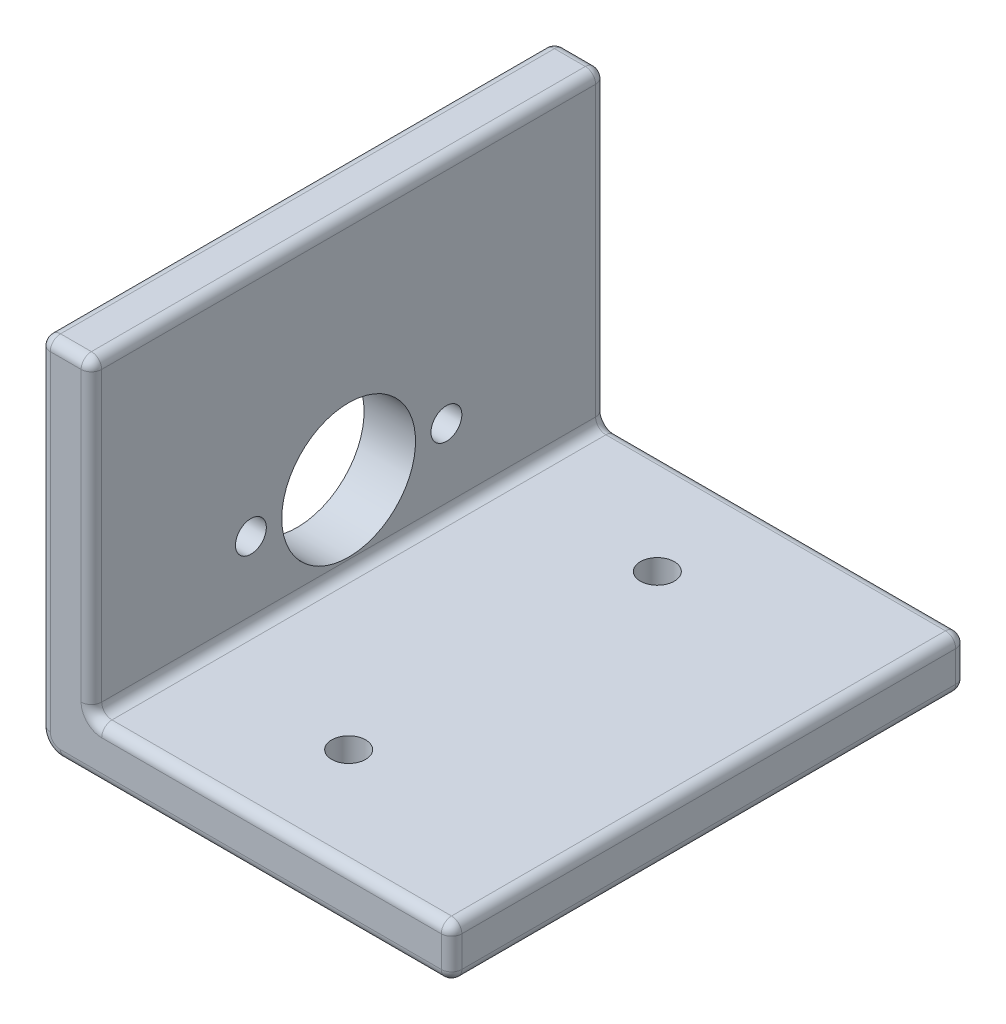
SolidWorks part; units mm, degrees
ref_plane "Front Plane" through (0, 0, 0) normal (0, 0, 1) x (1, 0, 0)
ref_plane "Top Plane" through (0, 0, 0) normal (0, 1, 0) x (1, 0, 0)
ref_plane "Right Plane" through (0, 0, 0) normal (1, 0, 0) x (0, 0, -1)
sketch "Sketch1" plane through (0, 0, 0) normal (0, 0, 1) x (1, 0, 0)
  line L2 (0, 0) -> (0, 35)
  line L3 (0, 35) -> (5, 35)
  line L4 (5, 5) -> (5, 35)
  line L5 (0, 0) -> (40, 0)
  line L7 (5, 5) -> (40, 5)
  line L8 (40, 0) -> (40, 5)
  dimension "D1" = 5
  dimension "D2" = 35
  dimension "D3" = 5
  dimension "D4" = 40
  dimension "D5" = 5
  dimension "D6" = 5
extrude "Boss-Extrude1" add sketch "Sketch1" along normal blind 50
fillet "Fillet1" radius 2 1 edges at (0, 0, 25)
sketch "Sketch2" plane through (0, 0, 0) normal (-1, 0, 0) x (0, 0, 1)
  line L0 (50, 0) -> (0, 0) construction
  line L2 (25, 75.5846) -> (25, -5.5846) construction
  line L7 (0, 35) -> (0, 2)
  line L8 (0, 2) -> (50, 2)
  line L9 (50, 2) -> (50, 35)
  line L10 (50, 35) -> (0, 35)
  line L11 (0, 35) -> (0, 2)
  line L12 (0, 2) -> (50, 2)
  line L13 (50, 2) -> (50, 35)
  line L14 (50, 35) -> (0, 35)
  circle A0 centre (25, 12.7) radius 6.5
  circle A1 centre (15.5, 12.7) radius 1.5
  circle A2 centre (34.5, 12.7) radius 1.5
  point P12 (25, 35)
  dimension "D1" = 13
  dimension "D2" = 12.7
  dimension "D3" = 0
  dimension "D6" = 3
  dimension "D7" = 3
  dimension "D4" = 19
  dimension "D5" = 9.5
extrude "Cut-Extrude1" cut sketch "Sketch2" against normal blind 20 contours L2 A0 | A0 L2 | A1 | A2 region at (0, 12.7, 27.7587) region at (0, 12.7, 22.2413) region at (0, 12.7, 15.5) region at (0, 12.7, 34.5)
sketch "Sketch3" plane through (0, 5, 0) normal (0, 1, 0) x (1, 0, 0)
  line L3 (-4.1123, -25) -> (84.1123, -25) construction
  line L7 (40, -50) -> (40, 0) construction
  line L9 (40, -50) -> (40, 0)
  line L10 (40, 0) -> (5, 0) construction
  line L11 (40, -50) -> (5, -50) construction
  line L12 (5, -50) -> (5, 0) construction
  line L13 (40, 0) -> (5, 0)
  line L14 (40, -50) -> (5, -50)
  line L15 (5, -50) -> (5, 0)
  circle A0 centre (20, -10) radius 1.65
  circle A1 centre (20, -40) radius 1.65
  point P18 (40, -25)
  dimension "D1" = 3.3
  dimension "D3" = 20
  dimension "D2" = 15
extrude "Cut-Extrude2" cut sketch "Sketch3" against normal blind 20 contours A0 | A1 region at (20, 5, 10) region at (20, 5, 40)
fillet "Fillet2" radius 1 1 edges at (5, 5, 25)
fillet "Fillet3" radius 1 20 edges at (21, 0, 0) (0.5858, 0.5858, 0) (23, 5, 0) (5.2929, 5.2929, 0) (21, 0, 50) (0.5858, 0.5858, 50) (23, 5, 50) (5.2929, 5.2929, 50) (0, 18.5, 0) (5, 20.5, 0) (0, 18.5, 50) (5, 20.5, 50) (5, 35, 25) (0, 35, 25) (40, 0, 25) (40, 5, 25) (40, 2.5, 0) (40, 2.5, 50) (2.5, 35, 50) (2.5, 35, 0)
